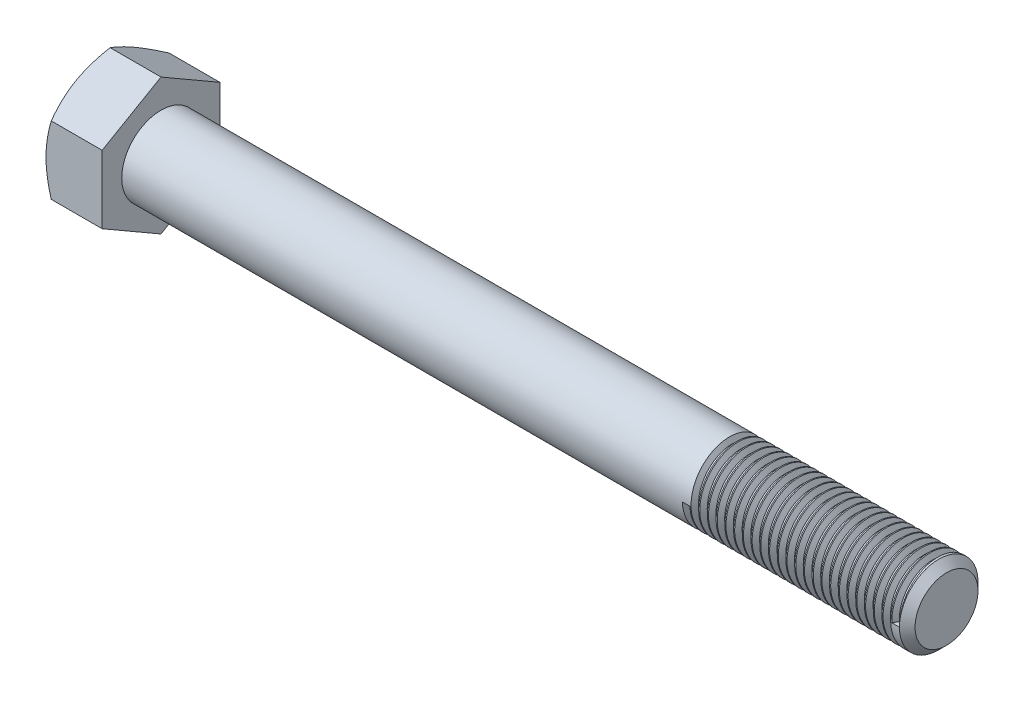
SolidWorks part; units mm, degrees
extrude "BaseHead" add sketch "Sketch1" along normal blind 6.8072
sketch "Sketch1" plane through (0, 0, 0) normal (1, 0, 0) x (0, 0, -1)
  line L0 (7.1374, 4.1208) -> (7.1374, -4.1208)
  line L1 (-7.1374, 4.1208) -> (-7.1374, -4.1208)
  line L2 (7.1374, -4.1208) -> (0, -8.2416)
  line L3 (0, -8.2416) -> (-7.1374, -4.1208)
  line L4 (7.1374, 4.1208) -> (0, 8.2416)
  line L5 (0, 8.2416) -> (-7.1374, 4.1208)
  dimension "D2" = 120
  dimension "D3" = 7.1374
  dimension "D4" = 7.1374
  dimension "D5" = 7.1374
ref_plane "Plane1" through (0, 0, 0) normal (0, 0, 1) x (1, 0, 0)
ref_plane "Plane2" through (0, 0, 0) normal (0, 1, 0) x (1, 0, 0)
ref_plane "Plane3" through (0, 0, 0) normal (1, 0, 0) x (0, 0, -1)
sketch "BodySke" plane through (0, 0, 0) normal (0, 0, 1) x (1, 0, 0)
  line L0 (0, 4.1208) -> (0, -4.1208) construction
  line L1 (0, 0) -> (102.0572, 0)
  line L2 (0, 0) -> (0, 4.7625)
  line L3 (0, 4.7625) -> (101.111, 4.7625)
  line L4 (102.0572, 0) -> (102.0572, 3.8163)
  line L5 (6.8072, 8.2416) -> (6.8072, 4.1208) construction
  line L6 (102.0572, 3.8163) -> (101.111, 4.7625)
  line L7 (0, 0) -> (96.52, 0) construction
  line L8 (102.0572, -3.8163) -> (101.111, -4.7625) construction
  line L9 (0, -4.7625) -> (101.111, -4.7625) construction
  line L10 (8.3947, 15.24) -> (8.3947, -2.54) construction
  line L11 (76.6572, 15.24) -> (76.6572, -2.54) construction
  line L12 (6.8072, 4.1208) -> (6.8072, -4.1208) construction
  dimension "Diameter" = 9.525
  dimension "Advance" = 1.5875
revolve "BaseBody" add sketch "BodySke" angle 360 about L7
cosmetic thread "ThreadCosmetic" [suppressed] parameters "Thread_length"=25.4, "Thread_minor"=7.6327
sketch "Sketch3" plane through (0, 0, 0) normal (0, 0, 1) x (1, 0, 0)
  line L0 (0, 7.1374) -> (4.3037, 14.5916)
  line L1 (0, 8.2416) -> (0, 4.1208) construction
  line L2 (4.3037, 14.5916) -> (4.3037, 20.9416)
  line L3 (4.3037, 20.9416) -> (-12.7, 20.9416)
  line L4 (-12.7, 20.9416) -> (-12.7, 7.1374)
  line L5 (-12.7, 7.1374) -> (0, 7.1374)
  line L6 (0, 0) -> (99.06, 0) construction
  line L7 (6.8072, 8.2416) -> (0, 8.2416) construction
  dimension "D1" = 7.1374
  dimension "D2" = 6.35
  dimension "D3" = 12.7
  dimension "D4" = 6.35
  dimension "Head_ch_ang" = 30
revolve "HeadChamfer" cut sketch "Sketch3" angle 360 about L6
fillet "HeadFillet" [suppressed] radius 0.762
sketch "ThdSchSke" plane through (0, 0, 0) normal (0, 0, 1) x (1, 0, 0)
  line L0 (76.6572, -3.8163) -> (75.9947, -4.7625)
  line L1 (76.6572, -3.8163) -> (77.3197, -4.7625)
  line L2 (77.3197, -4.7625) -> (77.3197, -5.9531)
  line L3 (-3.175, 0) -> (5.1513, 0) construction
  line L5 (77.3197, -5.9531) -> (75.9947, -5.9531)
  line L6 (75.9947, -5.9531) -> (75.9947, -4.7625)
  dimension "Thread_minor" = 7.6327
  dimension "Diameter" = 9.525
  dimension "Start" = 76.6572
revolve "ThreadSchematic" [suppressed] cut sketch "ThdSchSke" angle 360 about L3
pattern_linear "ThdSchPat" [suppressed]
thread "Thread1" pitch 1.0583 method cut profile "Thread Profile1" start angle 0, offset 0, length 25.4, pitch 1.0583, diameter 9.525
ref_plane "Plane4" through (101.111, 0, 4.7625) normal (0, -1, 0) x (0, 0, 1)
sketch "Thread Profile1" plane through (101.111, 0, 4.7625) normal (0, -1, 0) x (0, 0, 1)
  line L0 (0, 0) -> (0, 1.0583) construction
  line L11 (0, 0) -> (0, 0.926)
  line L12 (0, 0.926) -> (-0.5728, 0.5953)
  line L13 (-0.5728, 0.5953) -> (-0.5728, 0.3307)
  line L15 (-0.5728, 0.3307) -> (0, 0)
  line L17 (-0.5728, 0.463) -> (0, 0.463) construction
  point P2 (0, 0)
  dimension "Pitch" = 1.0583
  dimension "Profile_Angle" = 60
  dimension "Profile_Land" = 0.2646
  dimension "Profile_Height" = 0.5728
equation "\"D3@Sketch1\" = \"Width_flats@Sketch1\" / 2"
equation "\"D4@Sketch1\" = \"D3@Sketch1\""
equation "\"D5@Sketch1\" = \"D4@Sketch1\""
equation "\"Thread_minor@ThreadCosmetic\" = \"Minor_dia@BodySke\""
equation "\"D1@Sketch3\" = \"Width_flats@Sketch1\" / 2"
equation "\"Thread_length@ThreadCosmetic\" = ((sgn( (\"Length@BodySke\" - \"Advance@BodySke\" ) - \"Thread_nom@BodySke\" )-1)*( (\"Length@BodySke\" - \"Advance@BodySke\" ) - \"Thread_nom@BodySke\" ))/-2+ \"Thread_nom@BodySke\""
equation "\"Thread_minor@ThdSchSke\" = \"Minor_dia@BodySke\""
equation "\"Diameter@ThdSchSke\" = \"Diameter@BodySke\""
equation "\"Overcut@ThdSchSke\" = \"Diameter@BodySke\" * 1.25"
equation "\"Start@ThdSchSke\" = \"Head_ht@BaseHead\" + \"Length@BodySke\" - \"Thread_length@ThreadCosmetic\"  '---Non-countersunk---"
equation "\"Num_threads@ThdSchPat\" = int( \"Thread_length@ThreadCosmetic\" / \"Advance@BodySke\" + 0.999 )  + 1"
equation "\"Advance@ThdSchPat\" = \"Thread_length@ThreadCosmetic\" /  (\"Num_threads@ThdSchPat\" - 1) 'relax it"
equation "\"Num_threads@ThdSchPat\" = \"Num_threads@ThdSchPat\" - sgn( \"Num_threads@ThdSchPat\" - 1) '---chamfered tips only---"
